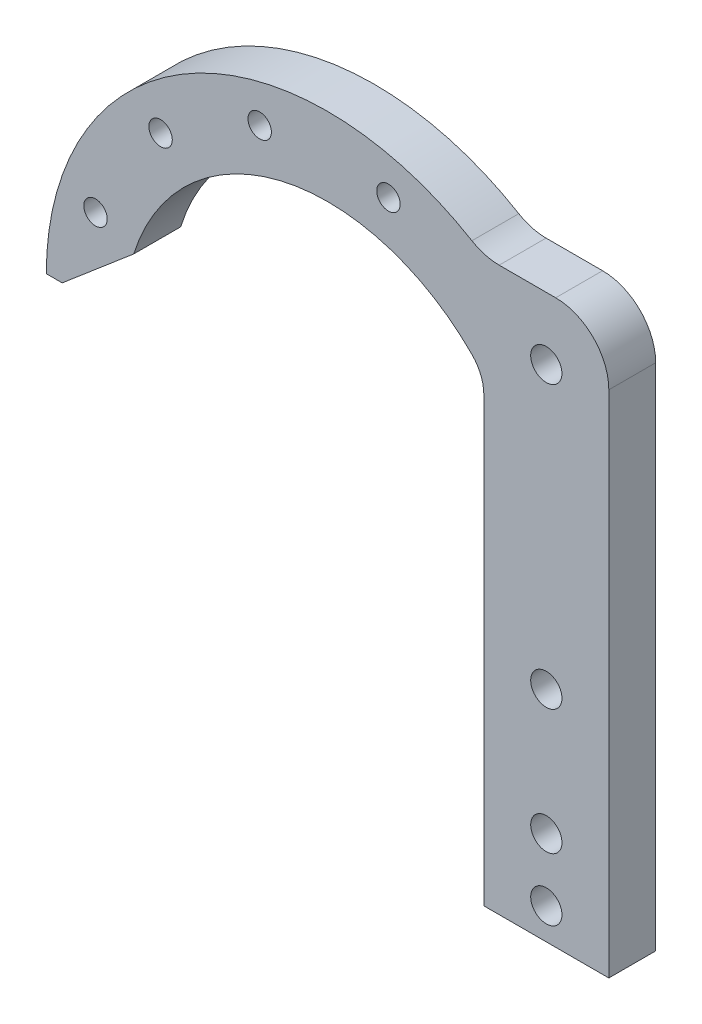
SolidWorks part; units mm, degrees
material "6063-T1"
ref_plane "Front Plane" through (0, 0, 0) normal (0, 0, 1) x (1, 0, 0)
ref_plane "Top Plane" through (0, 0, 0) normal (0, 1, 0) x (1, 0, 0)
ref_plane "Right Plane" through (0, 0, 0) normal (1, 0, 0) x (0, 0, -1)
sketch "Sketch1" plane through (0, 0, 0) normal (0, 0, 1) x (1, 0, 0)
  line L0 (0, 57.15) -> (0, -57.15) construction
  line L1 (-12.7, 57.15) -> (12.7, 57.15)
  line L2 (-12.7, 57.15) -> (-12.7, -57.15)
  line L3 (-12.7, -57.15) -> (12.7, -57.15)
  line L4 (12.7, 57.15) -> (12.7, -57.15)
  line L5 (-12.7, 57.15) -> (12.7, -57.15) construction
  line L6 (-12.7, -57.15) -> (12.7, 57.15) construction
  line L7 (-101.6, 9.631) -> (12.7, 9.631) construction
  line L8 (-101.6, 9.631) -> (-85.725, 9.631)
  line L10 (12.7, -14.7451) -> (12.7, -143.545) construction
  circle A0 centre (-44.45, 9.631) radius 57.15
  circle A1 centre (-44.45, 9.631) radius 41.275
  point P0 (0, 0)
  dimension "D3" = 114.3
  dimension "D4" = 82.55
  dimension "D1" = 25.4
  dimension "D2" = 114.3
extrude "Boss-Extrude1" add sketch "Sketch1" along normal blind 9.525 contours A1 L2 A0 L8 | A0 L4 L1 | A1 L2 A0 | L2 A1 | A0 L2 L3 L4 region at (-0.6607, 9.631, 0) region at (5.4947, 45.862, 0) region at (-13.7569, 46.5772, 0) region at (-8.8496, 9.631, 0) region at (2.322, -38.679, 0)
fillet "Fillet1" radius 8.255 1 edges at (-12.7, 36.0045, 4.7625)
chamfer "Chamfer1" distance 15.24 angle 48 1 edges at (-85.725, 9.631, 4.7625) first distance on face at (-93.6625, 9.631, 4.7625)
fillet "Fillet3" radius 10.795 2 edges at (-12.7, 57.15, 4.7625) (12.7, 57.15, 4.7625)
sketch "Sketch2" plane through (0, 0, 9.525) normal (0, 0, 1) x (1, 0, 0)
  line L0 (-12.7, -57.15) -> (12.7, -57.15) construction
  circle A0 centre (0, -50.8) radius 3.175
  circle A1 centre (0, -38.1) radius 3.175
  dimension "D3" = 6.35
  dimension "D4" = 6.35
  dimension "D1" = 6.35
  dimension "D2" = 12.7
extrude "Cut-Extrude1" cut sketch "Sketch2" against normal through all
sketch "Sketch3" plane through (0, 0, 9.525) normal (0, 0, 1) x (1, 0, 0)
  line L1 (-9.5789, 57.15) -> (1.905, 57.15) construction
  circle A0 centre (0, -12.7) radius 3.175
  circle A1 centre (0, -38.1) radius 3.175 construction
  circle A2 centre (0, 44.45) radius 3.175
  circle A3 centre (-91.6009, 25.4216) radius 2.3813
  circle A4 centre (-78.3809, 45.9799) radius 2.3813
  circle A5 centre (-58.2397, 57.4053) radius 2.3812
  circle A6 centre (-32.074, 57.7909) radius 2.3813
  circle A7 centre (-44.45, 9.631) radius 49.7247 construction
  arc A8 (-15.0813, 38.6327) -> (-83.8304, 21.9924) centre (-44.45, 9.631) ccw construction
  point P22 (-32.074, 57.4053)
  dimension "D1" = 6.35
  dimension "D3" = 6.35
  dimension "D5" = 4.7625
  dimension "D6" = 4.7625
  dimension "D7" = 4.7625
  dimension "D8" = 4.7625
  dimension "D2" = 25.4
  dimension "D4" = 12.7
extrude "Cut-Extrude2" cut sketch "Sketch3" against normal through all
